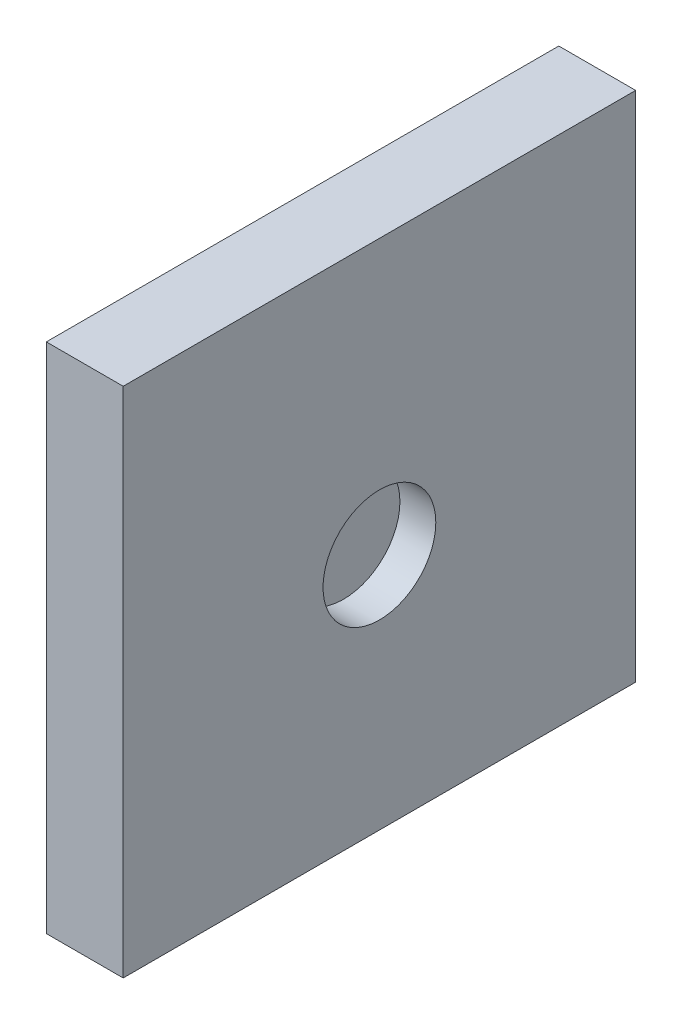
SolidWorks part; units mm, degrees
ref_plane "Alzado" through (0, 0, 0) normal (0, 0, 1) x (1, 0, 0)
ref_plane "Planta" through (0, 0, 0) normal (0, 1, 0) x (1, 0, 0)
ref_plane "Vista lateral" through (0, 0, 0) normal (1, 0, 0) x (0, 0, -1)
sketch "Croquis1" plane through (0, 0, 0) normal (1, 0, 0) x (0, 0, -1)
  line L1 (50, -50) -> (-50, -50)
  line L2 (50, -50) -> (50, 50)
  line L3 (50, 50) -> (-50, 50)
  line L4 (-50, -50) -> (-50, 50)
  line L5 (50, -50) -> (-50, 50) construction
  line L6 (50, 50) -> (-50, -50) construction
  point P0 (0, 0)
  dimension "D1" = 100
  dimension "D2" = 100
extrude "Saliente-Extruir1" add sketch "Croquis1" along normal blind 15
sketch "Croquis3" plane through (15, 0, 0) normal (1, 0, 0) x (0, 0, -1)
  line L0 (-50, -50) -> (50, -50) construction
  circle A0 centre (0, -3.5) radius 11
  dimension "D2" = 22
  dimension "D1" = 46.5
extrude "Cortar-Extruir1" cut sketch "Croquis3" against normal blind 7
